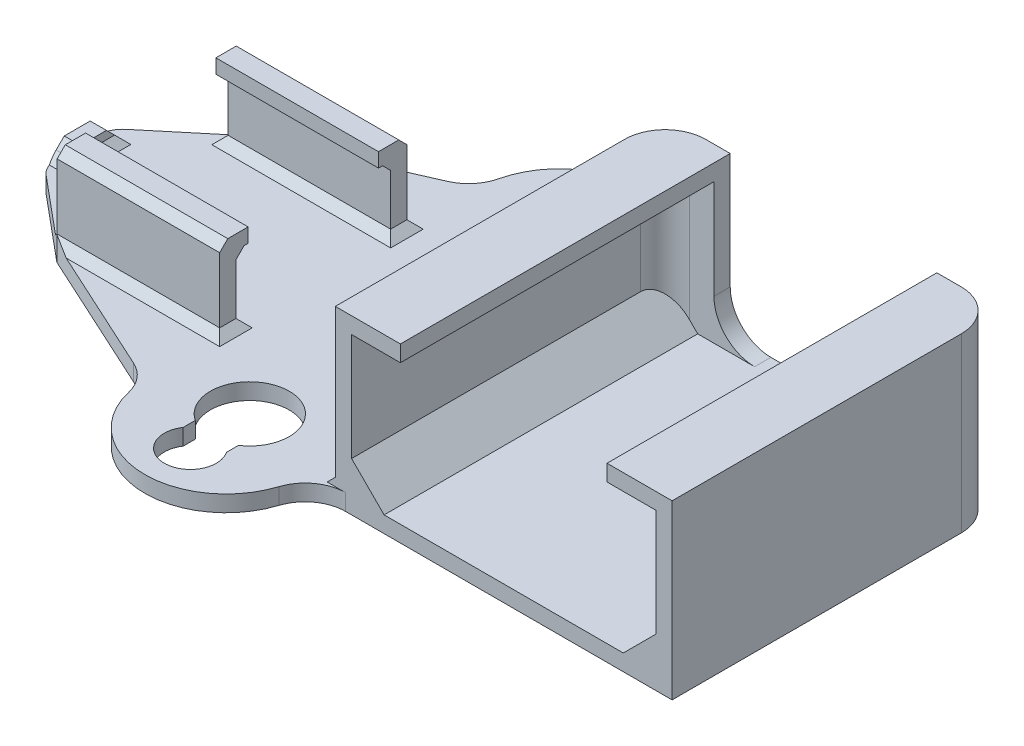
SolidWorks part; units mm, degrees
ref_plane "Front Plane" through (0, 0, 0) normal (0, 0, 1) x (1, 0, 0)
ref_plane "Top Plane" through (0, 0, 0) normal (0, 1, 0) x (1, 0, 0)
ref_plane "Right Plane" through (0, 0, 0) normal (1, 0, 0) x (0, 0, -1)
sketch "Sketch1" plane through (0, 0, 0) normal (0, 1, 0) x (1, 0, 0)
  line L0 (1.6716, 17.1781) -> (1.6716, -5.8219) construction
  line L1 (-11.9265, 14.1796) -> (-8.3284, 17.1781)
  line L2 (21.6629, -19.4069) -> (21.6629, -12.0976)
  line L3 (11.6716, -5.8219) -> (-8.3284, -5.8219) construction
  line L4 (76.0716, 25.9512) -> (76.0716, -14.595)
  line L5 (-17.3284, 8.273) -> (-17.3284, 3.0832)
  line L6 (-11.9265, 14.1796) -> (-16.2489, 10.5776)
  line L7 (-16.2489, 0.7785) -> (-11.9265, -2.8235)
  line L8 (1.6716, 5.6781) -> (-25.0675, 5.6781) construction
  line L9 (24.3206, -17.6245) -> (24.3206, -16.1442)
  line L10 (19.0053, -17.6245) -> (19.0053, -16.1442)
  line L11 (24.3206, 22.8677) -> (24.3206, 24.3481)
  line L12 (19.0053, 22.8677) -> (19.0053, 24.3481)
  line L13 (21.6629, 21.9934) -> (21.6629, 29.3026)
  line L14 (36.6716, 25.9512) -> (36.6716, -14.595) construction
  line L17 (-8.3284, 17.1781) -> (9.0724, 24.8143)
  line L18 (11.6716, 17.1781) -> (-8.3284, 17.1781) construction
  line L19 (-11.9265, -2.8235) -> (-8.3284, -5.8219)
  line L20 (-8.3284, -5.8219) -> (9.1456, -13.8508)
  line L21 (74.0716, 25.9512) -> (74.0716, -14.595) construction
  line L22 (36.6716, 25.9512) -> (76.0716, 25.9512)
  line L23 (36.6716, -14.595) -> (76.0716, -14.595)
  line L24 (36.6716, 25.9512) -> (35.8051, 25.9512)
  line L25 (36.6716, -14.595) -> (35.9542, -14.595)
  arc A0 (19.0053, -17.6245) -> (24.3206, -17.6245) centre (21.6629, -19.4069) ccw
  arc A1 (24.3206, -16.1442) -> (19.0053, -16.1442) centre (21.6629, -12.0976) ccw
  arc A2 (24.3206, 24.3481) -> (19.0053, 24.3481) centre (21.6629, 28.3947) ccw
  arc A3 (19.0053, 22.8677) -> (24.3206, 22.8677) centre (21.6629, 21.0854) ccw
  arc A4 (31.091, 29.2845) -> (11.9297, 28.2456) centre (21.6629, 25.9512) ccw
  arc A5 (11.9292, -17.2666) -> (31.1933, -18.0671) centre (21.6716, -15.0114) ccw
  arc A6 (11.9292, -17.2666) -> (9.1456, -13.8508) centre (7.058, -18.3941) ccw
  arc A7 (9.0724, 24.8143) -> (11.9297, 28.2456) centre (7.0631, 29.3928) ccw
  arc A8 (-16.2489, 0.7785) -> (-17.3284, 3.0832) centre (-14.3284, 3.0832) cw
  arc A9 (-16.2489, 10.5776) -> (-17.3284, 8.273) centre (-14.3284, 8.273) ccw
  arc A10 (31.1933, -18.0671) -> (35.9542, -14.595) centre (35.9542, -19.595) cw
  arc A11 (31.091, 29.2845) -> (35.8051, 25.9512) centre (35.8051, 30.9512) ccw
  point P30 (11.6629, 25.9512)
  point P35 (-17.3284, 1.6781)
  point P38 (-17.3284, 9.6781)
  dimension "D1" = 5
  dimension "D2" = 3
  dimension "D7" = 5
  dimension "D3" = 19
  dimension "D4" = 8
  dimension "D5" = 25
  dimension "D6" = 37.4
  dimension "D8" = 2
extrude "Boss-Extrude3" add sketch "Sketch1" along normal blind 2 contours L6 A9 L5 A8 L7 A5 A4 A1 L9 A0 L10 A3 L12 A2 L11 region at (33.3901, 0, -5.5737)
sketch "Sketch2" plane through (0, 2, 0) normal (0, 1, 0) x (1, 0, 0)
  line L1 (-17.3284, 8.273) -> (-15.3284, 8.273)
  line L2 (-17.3284, 8.273) -> (-17.3284, 3.0832)
  line L3 (-17.3284, 3.0832) -> (-15.3284, 3.0832)
  line L4 (-15.3284, 8.273) -> (-15.3284, 3.0832)
  line L5 (11.6543, 17.2264) -> (-8.3284, 17.2264)
  line L6 (11.6543, 17.2264) -> (11.6543, 15.2264)
  line L7 (11.6543, 15.2264) -> (-8.3284, 15.2264)
  line L8 (-8.3284, 17.2264) -> (-8.3284, 15.2264)
  line L9 (11.6629, 25.9512) -> (11.6716, -15.0114) construction
  line L10 (11.6519, -5.7923) -> (-8.3284, -5.7923)
  line L11 (11.6519, -5.7923) -> (11.6519, -3.7923)
  line L12 (11.6519, -3.7923) -> (-8.3284, -3.7923)
  line L13 (-8.3284, -5.7923) -> (-8.3284, -3.7923)
  line M35 (9.0724, 24.8143) -> (-8.3284, 17.1781)
  dimension "D1" = 2
  dimension "D2" = 2
  dimension "D3" = 2
extrude "Boss-Extrude4" add sketch "Sketch2" along normal blind 10 contours L8 L7 L6 L5 M35 | L13 L10 L11 L12 region at (1.6636, 2, -16.2264) region at (1.6618, 2, 4.7923)
sketch "Sketch4" plane through (0, 0, -15.2264) normal (0, 0, 1) x (1, 0, 0)
  line L0 (11.6543, 12) -> (11.6543, 2) construction
  line L1 (-8.3284, 12) -> (11.6543, 12)
  line L2 (-8.3284, 12) -> (-8.3284, 10.25)
  line L3 (-8.3284, 10.25) -> (11.6543, 10.25)
  line L4 (11.6543, 12) -> (11.6543, 10.25)
  dimension "D1" = 1.75
extrude "Boss-Extrude6" add sketch "Sketch4" along normal blind 1.5
sketch "Sketch5" plane through (0, 0, 3.7923) normal (0, 0, -1) x (-1, 0, 0)
  line L1 (8.3284, 12) -> (-11.6519, 12)
  line L2 (8.3284, 12) -> (8.3284, 10.25)
  line L3 (8.3284, 10.25) -> (-11.6519, 10.25)
  line L4 (-11.6519, 12) -> (-11.6519, 10.25)
  dimension "D1" = 1.75
extrude "Boss-Extrude7" add sketch "Sketch5" along normal blind 1.5
sketch "Sketch6" plane through (0, 2, 0) normal (0, 1, 0) x (1, 0, 0)
  line L0 (35.8051, 25.9512) -> (76.0716, 25.9512) construction
  line L1 (76.0716, -14.595) -> (35.9542, -14.595) construction
  line L4 (36.6716, 25.9512) -> (34.6716, 25.9512)
  line L5 (36.6716, 25.9512) -> (36.6716, -14.595)
  line L6 (36.6716, -14.595) -> (34.6716, -14.595)
  line L7 (34.6716, 25.9512) -> (34.6716, -14.595)
  line L8 (76.0716, 25.9512) -> (74.0716, 25.9512)
  line L9 (76.0716, 25.9512) -> (76.0716, -14.595)
  line L10 (76.0716, -14.595) -> (74.0716, -14.595)
  line L11 (74.0716, 25.9512) -> (74.0716, -14.595)
  dimension "D1" = 2
  dimension "D2" = 37.4
  dimension "D3" = 2
extrude "Boss-Extrude8" add sketch "Sketch6" along normal blind 19.2
sketch "Sketch7" plane through (74.0716, 0, 0) normal (-1, 0, 0) x (0, 0, 1)
  line L0 (-25.9512, 21.2) -> (-25.9512, 2) construction
  line L1 (14.595, 21.2) -> (-25.9512, 21.2)
  line L2 (14.595, 21.2) -> (14.595, 19.2)
  line L3 (14.595, 19.2) -> (-25.9512, 19.2)
  line L4 (-25.9512, 21.2) -> (-25.9512, 19.2)
  dimension "D1" = 2
extrude "Boss-Extrude9" add sketch "Sketch7" along normal blind 6
sketch "Sketch8" plane through (36.6716, 0, 0) normal (1, 0, 0) x (0, 0, -1)
  line L0 (25.9512, 21.2) -> (25.9512, 2) construction
  line L1 (-14.595, 21.2) -> (25.9512, 21.2)
  line L2 (-14.595, 21.2) -> (-14.595, 19.2)
  line L3 (-14.595, 19.2) -> (25.9512, 19.2)
  line L4 (25.9512, 21.2) -> (25.9512, 19.2)
  dimension "D1" = 2
extrude "Boss-Extrude10" add sketch "Sketch8" along normal blind 6
sketch "Sketch9" plane through (36.6716, 0, 0) normal (1, 0, 0) x (0, 0, -1)
  line L0 (-14.595, 2) -> (25.9512, 2) construction
  line L1 (25.9512, 19.2) -> (23.9512, 19.2)
  line L2 (25.9512, 19.2) -> (25.9512, 2)
  line L3 (25.9512, 2) -> (23.9512, 2)
  line L4 (23.9512, 19.2) -> (23.9512, 2)
  dimension "D1" = 2
extrude "Boss-Extrude11" add sketch "Sketch9" along normal up to vertex (6 mm away) up to point (42.6716, 19.2, 14.595)
sketch "Sketch11" plane through (74.0716, 0, 0) normal (-1, 0, 0) x (0, 0, 1)
  line L1 (-25.9512, 2) -> (14.595, 2) construction
  line L2 (-25.9512, 19.2) -> (-23.9512, 19.2)
  line L3 (-25.9512, 19.2) -> (-25.9512, 2)
  line L4 (-25.9512, 2) -> (-23.9512, 2)
  line L6 (-23.9512, 19.2) -> (-23.9512, 2)
  dimension "D1" = 2
extrude "Boss-Extrude12" add sketch "Sketch11" along normal up to vertex (6 mm away) up to point (68.0716, 19.2, 14.595)
chamfer "Chamfer3" distance 1 angle 45 3 edges at (34.6716, 2, -5.6781) (1.6618, 2, 5.7923)
fillet "Fillet6" radius 3 2 edges at (74.0716, 10.6, -23.9512) (36.6716, 10.6, -23.9512)
fillet "Fillet12" radius 5 2 edges at (76.0716, 10.6, -25.9512) (34.6716, 12.1, -25.9512)
fillet "Fillet13" radius 5 2 edges at (42.6716, 2, -24.9512) (68.0716, 2, -24.9512)
chamfer "Chamfer4" distance 4 angle 45 2 edges at (74.0716, 2, -3.1781) (36.6716, 2, -3.1781) tangent propagation no
sketch "Sketch12" plane through (0, 2, 0) normal (0, 1, 0) x (1, 0, 0)
  line L1 (-17.3284, 8.273) -> (-15.3284, 8.273)
  line L2 (-17.3284, 8.273) -> (-17.3284, 3.0832)
  line L3 (-17.3284, 3.0832) -> (-15.3284, 3.0832)
  line L4 (-15.3284, 8.273) -> (-15.3284, 3.0832)
  dimension "D1" = 2
extrude "Boss-Extrude13" add sketch "Sketch12" along normal blind 2
chamfer "Chamfer5" distance 1 angle 45 15 edges at (1.6618, 10.25, 3.7923) (1.663, 10.25, -15.2264) (1.718, 12, -17.2264) (1.6618, 12, 5.7923) (11.6543, 2, -16.7264) (1.663, 2, -15.2264) (-8.3284, 2, -16.2023) (11.6519, 2, 5.2923) (-8.3284, 2, 4.8071) (1.6618, 2, 3.7923) (-16.3284, 4, -3.0832) (-16.3284, 4, -8.273) (-16.3284, 2, -8.273) (-15.3284, 2, -5.6781) (-16.3284, 2, -3.0832)
